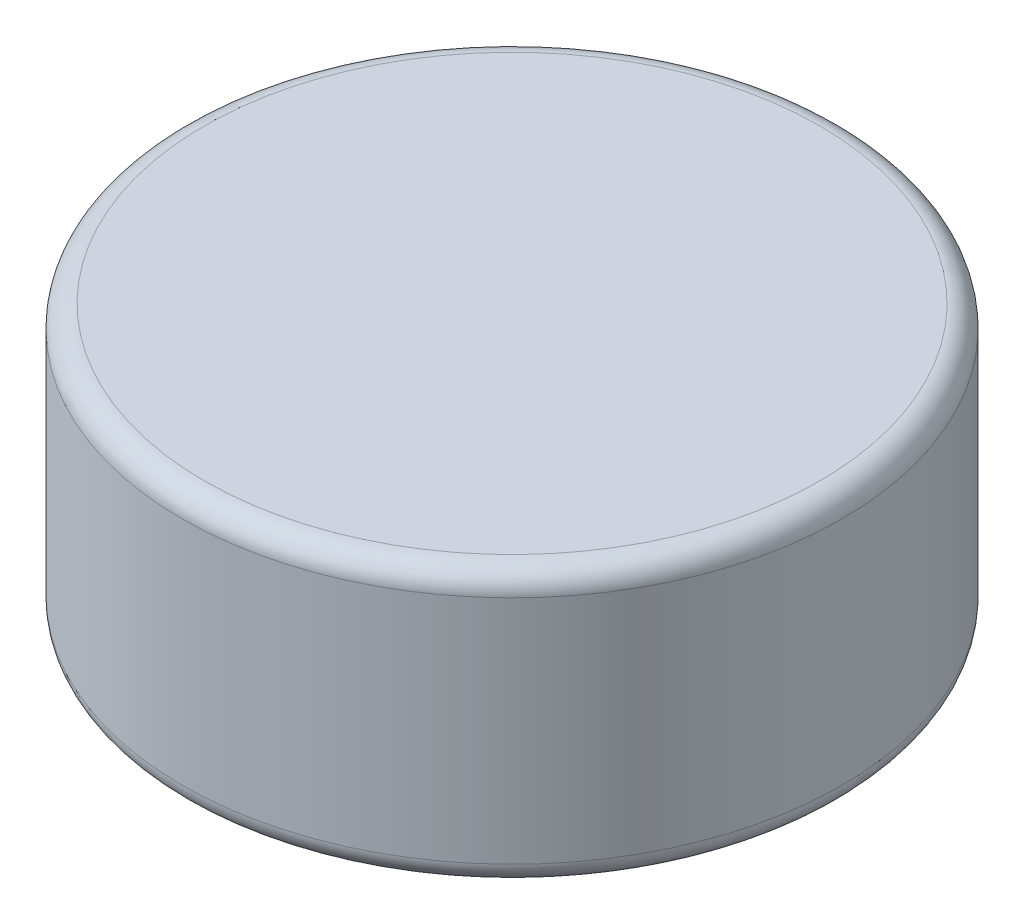
SolidWorks part; units mm, degrees
ref_plane "Front Plane" through (0, 0, 0) normal (0, 0, 1) x (1, 0, 0)
ref_plane "Top Plane" through (0, 0, 0) normal (0, 1, 0) x (1, 0, 0)
ref_plane "Right Plane" through (0, 0, 0) normal (1, 0, 0) x (0, 0, -1)
sketch "Sketch1" plane through (0, 0, 0) normal (0, 1, 0) x (1, 0, 0)
  circle A0 centre (0, 0) radius 3
  dimension "D1" = 6
extrude "Boss-Extrude1" add sketch "Sketch1" along normal mid plane 2.5
ref_axis "Axis1" through (0, 0, 0) along (0, 1, 0)
fillet "Fillet1" radius 0.2 2 edges at (0, -1.25, 3) (0, 1.25, 3)
